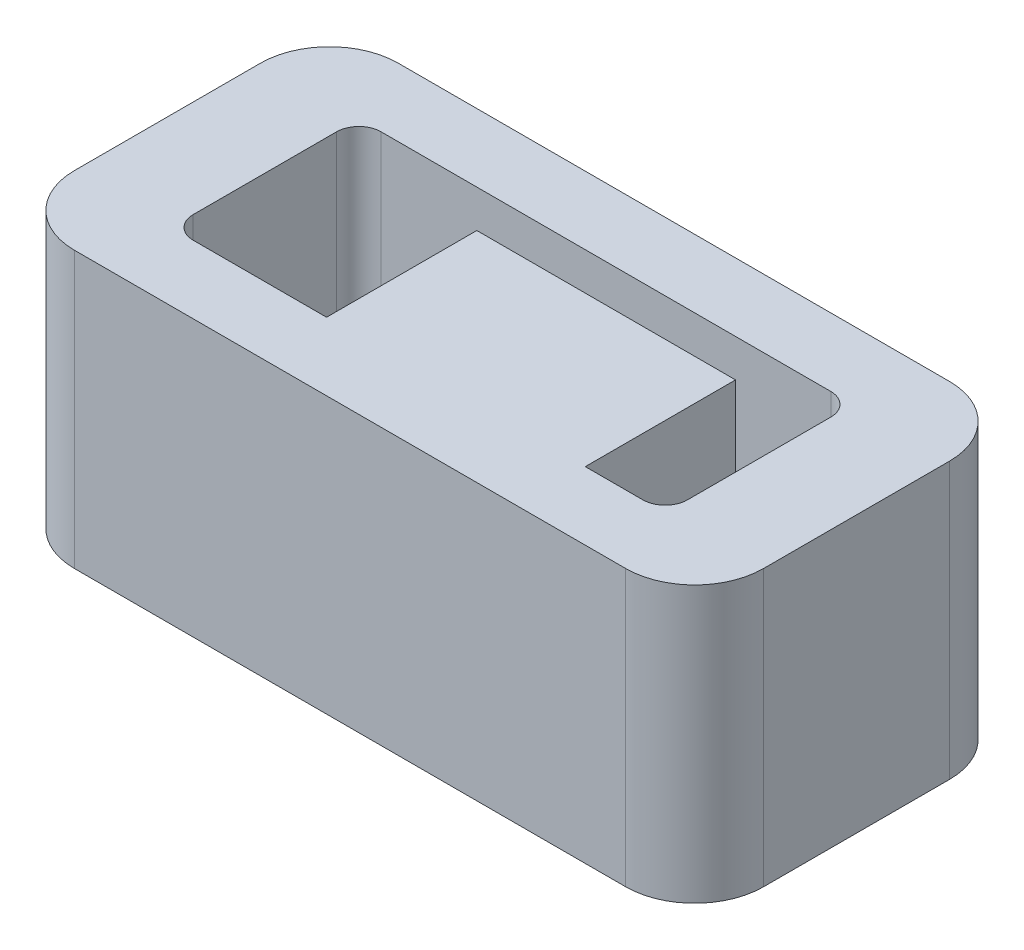
SolidWorks part; units mm, degrees
material "K110"
ref_plane "Front Plane" through (0, 0, 0) normal (0, 0, 1) x (1, 0, 0)
ref_plane "Top Plane" through (0, 0, 0) normal (0, 1, 0) x (1, 0, 0)
ref_plane "Right Plane" through (0, 0, 0) normal (1, 0, 0) x (0, 0, -1)
sketch "Sketch2" plane through (0, 0, 0) normal (0, 1, 0) x (1, 0, 0)
  line L1 (-50, -23.5) -> (50, -23.5)
  line L2 (-50, -23.5) -> (-50, 23.5)
  line L3 (-50, 23.5) -> (50, 23.5)
  line L4 (50, -23.5) -> (50, 23.5)
  line L5 (-50, -23.5) -> (50, 23.5) construction
  line L6 (-50, 23.5) -> (50, -23.5) construction
  point P0 (0, 0)
  dimension "D1" = 100
  dimension "D2" = 47
extrude "Boss-Extrude1" add sketch "Sketch2" against normal blind 40
fillet "Fillet1" radius 10 4 edges at (-50, -20, -23.5) (50, -20, -23.5) (50, -20, 23.5) (-50, -20, 23.5)
sketch "Sketch3" plane through (0, 0, 0) normal (0, 1, 0) x (1, 0, 0)
  line L16 (35.855, -10.4) -> (35.855, 10.4)
  line L17 (24.265, -13.63) -> (32.625, -13.63)
  line L18 (24.265, 8.17) -> (24.265, -13.63)
  line L19 (-13.275, 8.17) -> (24.265, 8.17)
  line L20 (-13.275, -13.63) -> (-13.275, 8.17)
  line L21 (-32.625, -13.63) -> (-13.275, -13.63)
  line L22 (-35.855, 10.4) -> (-35.855, -10.4)
  line L23 (32.625, 13.63) -> (-32.625, 13.63)
  line L24 (35.855, -10.4) -> (35.855, 10.4)
  line L25 (24.265, -13.63) -> (32.625, -13.63)
  line L26 (24.265, 8.17) -> (24.265, -13.63)
  line L27 (-13.275, 8.17) -> (24.265, 8.17)
  line L28 (-13.275, -13.63) -> (-13.275, 8.17)
  line L29 (-32.625, -13.63) -> (-13.275, -13.63)
  line L30 (-35.855, 10.4) -> (-35.855, -10.4)
  line L31 (32.625, 13.63) -> (-32.625, 13.63)
  arc A8 (35.855, 10.4) -> (32.625, 13.63) centre (32.625, 10.4) ccw
  arc A9 (32.625, -13.63) -> (35.855, -10.4) centre (32.625, -10.4) ccw
  arc A10 (-35.855, -10.4) -> (-32.625, -13.63) centre (-32.625, -10.4) ccw
  arc A11 (-32.625, 13.63) -> (-35.855, 10.4) centre (-32.625, 10.4) ccw
  arc A12 (35.855, 10.4) -> (32.625, 13.63) centre (32.625, 10.4) ccw
  arc A13 (32.625, -13.63) -> (35.855, -10.4) centre (32.625, -10.4) ccw
  arc A14 (-35.855, -10.4) -> (-32.625, -13.63) centre (-32.625, -10.4) ccw
  arc A15 (-32.625, 13.63) -> (-35.855, 10.4) centre (-32.625, 10.4) ccw
  dimension "D1" = 0.23
extrude "Cut-Extrude1" cut sketch "Sketch3" against normal up to next
hole_wizard "M6 Tapped Hole1" positions "Sketch6" profile "Sketch5" tap size "M6" standard "ISO"
sketch "Sketch6" plane through (0, -40, 0) normal (0, -1, 0) x (-1, 0, 0)
  line L0 (-50, -13.5) -> (-50, 13.5) construction
  line L1 (-40, 23.5) -> (40, 23.5) construction
  line L2 (40, -23.5) -> (-40, -23.5) construction
  line L3 (50, 13.5) -> (50, -13.5) construction
  point P0 (-43, 16.5)
  point P2 (43, 16.5)
  point P4 (43, -16.5)
  point P6 (-43, -16.5)
  dimension "D1" = 7
  dimension "D2" = 7
  dimension "D3" = 7
  dimension "D4" = 7
sketch "Sketch5" plane through (43, -40, -16.5) normal (1, 0, 0) x (0, 0, -1)
  line L0 (0, 0) -> (0, 18.5022)
  line L1 (0, 18.5022) -> (2.5, 17)
  line L2 (2.5, 17) -> (2.5, 0.525)
  line L3 (2.5, 0.525) -> (3.025, 0)
  line L5 (3.025, 0) -> (0, 0)
  line L6 (-2.5, 0.525) -> (-3.025, 0) construction
  line L10 (0, 18.5022) -> (-2.5, 17) construction
  line L11 (0, -6.35) -> (0, 107.95) construction
  dimension "Tap Drill Dia." = 5
  dimension "Tap Drill Depth" = 17
  dimension "Near C'Sink Dia." = 6.05
  dimension "Near C'Sink Angle" = 90
  dimension "Drill Angle" = 118
cosmetic thread "Hole Thread1"
cosmetic thread "Hole Thread2"
cosmetic thread "Hole Thread3"
cosmetic thread "Hole Thread4"
